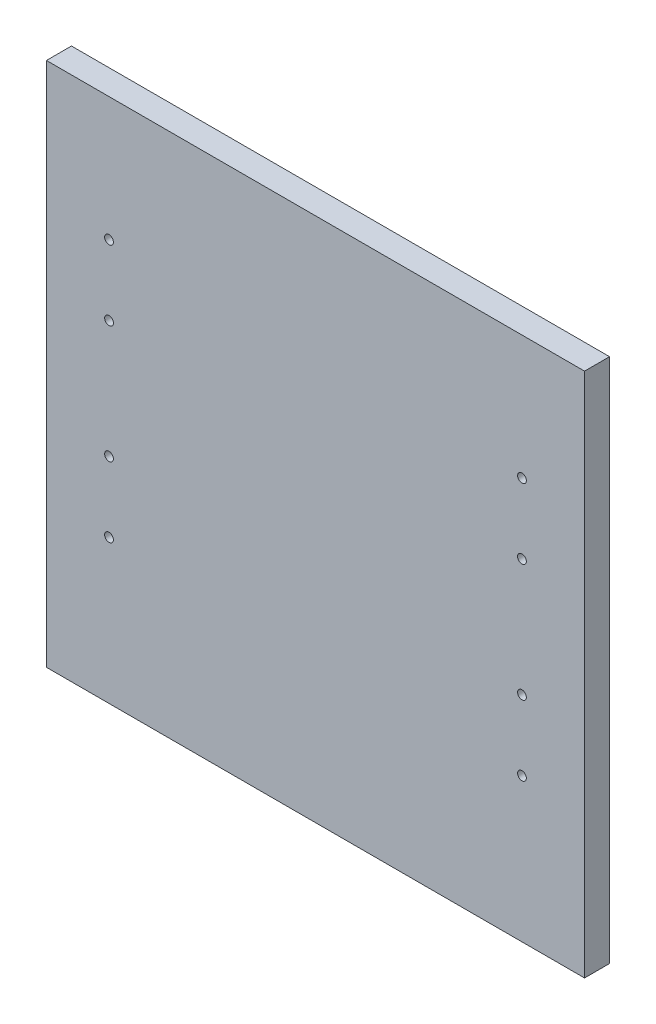
SolidWorks part; units mm, degrees
material "Органическое стекло СО-95-К ГОСТ 10667-90"
ref_plane "Спереди" through (0, 0, 0) normal (0, 0, 1) x (1, 0, 0)
ref_plane "Сверху" through (0, 0, 0) normal (0, 1, 0) x (1, 0, 0)
ref_plane "Справа" through (0, 0, 0) normal (1, 0, 0) x (0, 0, -1)
ref_axis "ОсьX" through (-88.99, 0, 0) along (1, 0, 0)
ref_axis "ОсьZ" through (0, 55, 0) along (0, -1, 0)
ref_axis "ОсьY" through (0, 0, -88.99) along (0, 0, 1)
sketch "Эскиз1" plane through (0, 0, 0) normal (0, 0, 1) x (1, 0, 0)
  line L1 (-215, 210) -> (215, 210)
  line L2 (-215, 210) -> (-215, -210)
  line L3 (-215, -210) -> (215, -210)
  line L4 (215, 210) -> (215, -210)
  line L5 (0, 65.4162) -> (0, -65.4075) construction
  line L6 (-215, 210) -> (-215, -210)
  line L7 (215, 210) -> (215, -210)
  line L8 (-159.2536, 8) -> (189.9089, 8) construction
  circle A0 centre (-165, 111) radius 3.5
  circle A1 centre (-165, 55) radius 3.5
  circle A8 centre (-165, -39) radius 3.5
  circle A9 centre (-165, -95) radius 3.5
  circle A16 centre (165, -95) radius 3.5
  circle A17 centre (165, -39) radius 3.5
  circle A18 centre (165, 55) radius 3.5
  circle A19 centre (165, 111) radius 3.5
  point P4 (0, 210)
  point P6 (-215, 0)
  dimension "D3" = 7
  dimension "D4" = 56
  dimension "D5" = 330
  dimension "D1" = 430
  dimension "D2" = 420
  dimension "D7" = 150
  dimension "D8" = 115
extrude "Бобышка-Вытянуть1" add sketch "Эскиз1" along normal blind 20 contours L4 L1 L2 L3 A8 A19 A17 A1 A0 A18 A9 region at (0, -0.0137, 0)
